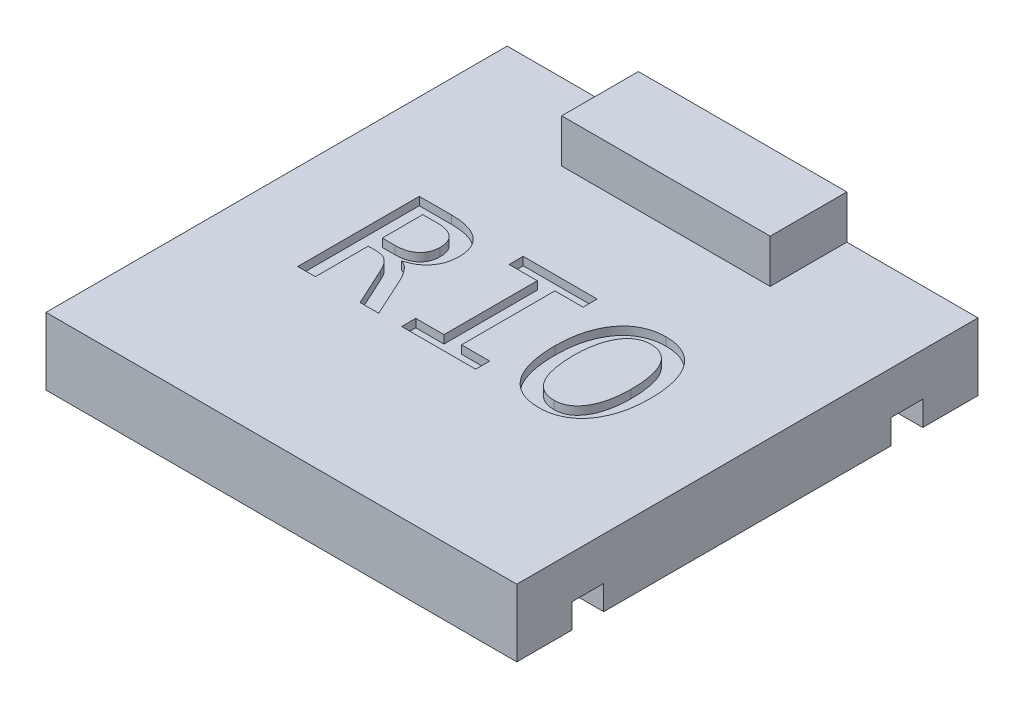
SolidWorks part; units mm, degrees
ref_plane "Front Plane" through (0, 0, 0) normal (0, 0, 1) x (1, 0, 0)
ref_plane "Top Plane" through (0, 0, 0) normal (0, 1, 0) x (1, 0, 0)
ref_plane "Right Plane" through (0, 0, 0) normal (1, 0, 0) x (0, 0, -1)
sketch "Sketch1" plane through (0, 0, 0) normal (0, 1, 0) x (1, 0, 0)
  line L1 (0, 0) -> (146.1516, 0)
  line L2 (0, 0) -> (0, 143.1798)
  line L3 (0, 143.1798) -> (146.1516, 143.1798)
  line L4 (146.1516, 0) -> (146.1516, 143.1798)
  dimension "D1" = 146.1516
  dimension "D2" = 143.1798
extrude "Boss-Extrude1" add sketch "Sketch1" along normal mid plane 34.417
sketch "Sketch3" plane through (0, 17.2085, 0) normal (0, 1, 0) x (1, 0, 0)
  line L0 (146.1516, 0) -> (146.1516, 143.1798) construction
  line L1 (0, 0) -> (146.1516, 0)
  line L2 (0, 0) -> (0, 119.38)
  line L3 (0, 119.38) -> (146.1516, 119.38)
  line L4 (146.1516, 0) -> (146.1516, 119.38)
  line L5 (146.1516, 143.1798) -> (0, 143.1798) construction
  line L6 (0, 119.38) -> (40.7162, 119.38)
  line L7 (0, 119.38) -> (0, 143.1798)
  line L8 (0, 143.1798) -> (40.7162, 143.1798)
  line L9 (40.7162, 119.38) -> (40.7162, 143.1798)
  line L11 (146.1516, 119.38) -> (105.4354, 119.38)
  line L12 (146.1516, 119.38) -> (146.1516, 143.1798)
  line L13 (146.1516, 143.1798) -> (105.4354, 143.1798)
  line L14 (105.4354, 119.38) -> (105.4354, 143.1798)
  line M1 (0, 143.1798) -> (0, 0)
  line M2 (0, 0) -> (146.1516, 0)
  line M3 (146.1516, 0) -> (146.1516, 143.1798)
  line M4 (146.1516, 143.1798) -> (0, 143.1798)
  dimension "D1" = 119.38
  dimension "D2" = 40.7162
extrude "Cut-Extrude2" cut sketch "Sketch3" against normal offset from surface (13.5128 mm away) 20.9042 contours L3 M1 M2 M3 | L3 L9 M4 M1 | L14 L3 M3 M4 region at (73.0758, 17.2085, -59.69) region at (20.3581, 17.2085, -131.2799) region at (125.7935, 17.2085, -131.2799) up to face at (73.0758, -17.2085, -71.5899)
sketch "Sketch2" plane through (0, 3.6957, 0) normal (0, 1, 0) x (1, 0, 0)
  text T0 "RIO" font "Consolas" height in points 144
extrude "Cut-Extrude1" cut sketch "Sketch2" against normal blind 2.54
sketch "Sketch4" plane through (146.1516, 0, 0) normal (1, 0, 0) x (0, 0, -1)
  line L0 (0, -17.2085) -> (143.1798, -17.2085) construction
  line L1 (17.145, -17.2085) -> (26.9748, -17.2085)
  line L2 (17.145, -17.2085) -> (17.145, -9.5885)
  line L3 (17.145, -9.5885) -> (26.9748, -9.5885)
  line L4 (26.9748, -17.2085) -> (26.9748, -9.5885)
  line L5 (143.1798, 3.6957) -> (143.1798, -17.2085) construction
  line L6 (126.0348, -17.2085) -> (116.205, -17.2085)
  line L7 (126.0348, -17.2085) -> (126.0348, -9.5885)
  line L8 (126.0348, -9.5885) -> (116.205, -9.5885)
  line L9 (116.205, -17.2085) -> (116.205, -9.5885)
  line L10 (0, 3.6957) -> (0, -17.2085) construction
  dimension "D1" = 9.8298
  dimension "D2" = 17.145
  dimension "D3" = 17.145
  dimension "D4" = 7.62
extrude "Cut-Extrude3" cut sketch "Sketch4" against normal blind 10.16
ref_plane "Plane1" through (73.0758, 0, 0) normal (-1, 0, 0) x (0, 0, 1)
mirror "Mirror1" about plane through (73.0758, 0, 0) normal (-1, 0, 0) of "Cut-Extrude3"
